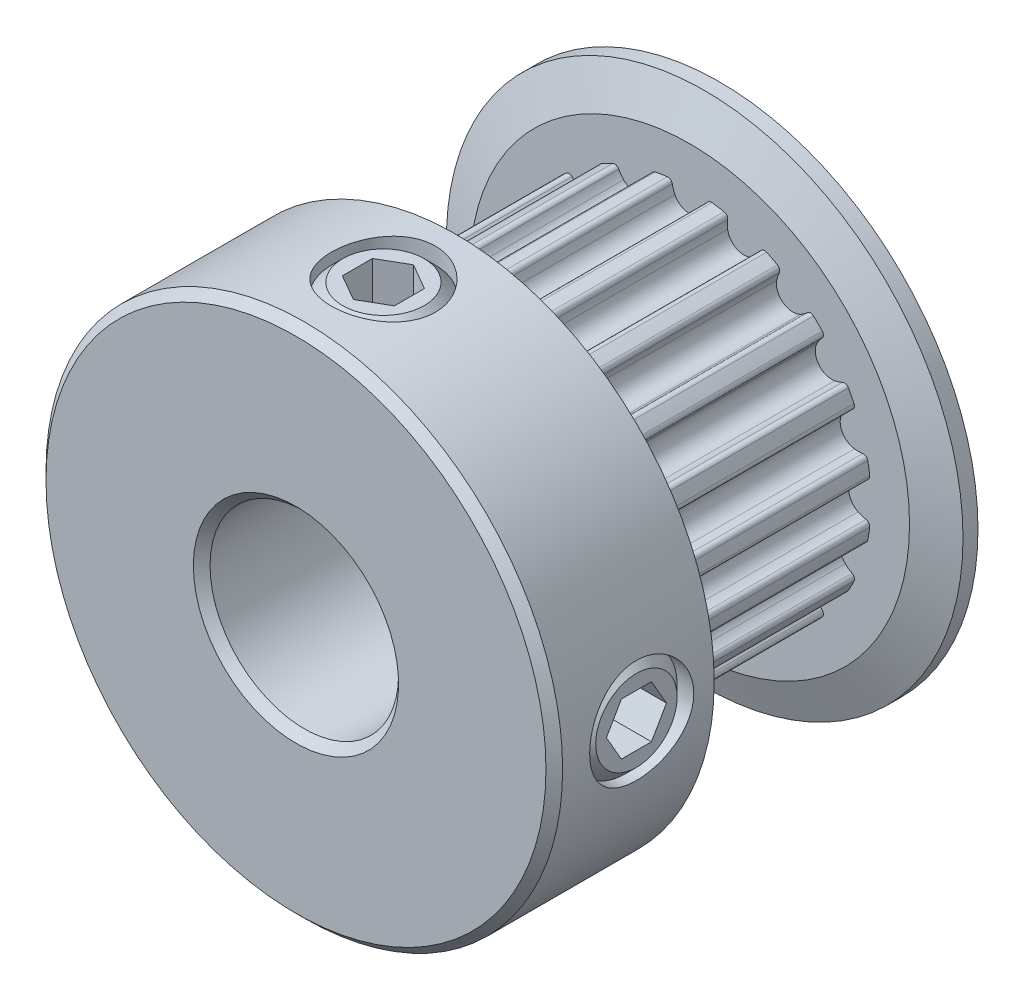
SolidWorks part; units mm, degrees
ref_plane "Front Plane" through (0, 0, 0) normal (0, 0, 1) x (1, 0, 0)
ref_plane "Top Plane" through (0, 0, 0) normal (0, 1, 0) x (1, 0, 0)
ref_plane "Right Plane" through (0, 0, 0) normal (1, 0, 0) x (0, 0, -1)
sketch "Sketch1" plane through (0, 0, 0) normal (0, 0, 1) x (1, 0, 0)
  line L1 (-1.7499, 5.3585) -> (1.7499, 5.3585) construction
  line L4 (0, 0) -> (0, 5.3585) construction
  line L5 (0, 5.3585) -> (0, 11.264) construction
  line L6 (0, 6.3625) -> (1.9751, 6.0482) construction
  line L7 (1.9751, 6.0482) -> (2.6648, 5.8229) construction
  line L8 (1.9751, 6.0482) -> (1.7499, 5.3585) construction
  line L9 (-1.9751, 6.0482) -> (-1.7499, 5.3585) construction
  line L10 (-1.8963, 5.8067) -> (-2.841, 8.6995)
  line L11 (-2.841, 8.6995) -> (2.841, 8.6995)
  line L12 (2.841, 8.6995) -> (1.8963, 5.8067)
  circle A0 centre (0, 0) radius 6.3625 construction
  circle A1 centre (0, 0) radius 8.6995 construction
  circle A2 centre (0, 0) radius 6.1085 construction
  arc A3 (-0.4989, 5.6703) -> (0.4989, 5.6703) centre (0, 5.9135) ccw
  arc A4 (-0.4989, 5.6703) -> (-0.5855, 5.9387) centre (0.4, 6.1085) cw
  arc A5 (-1.8963, 5.8067) -> (-0.7518, 6.0621) centre (0, 0) cw
  arc A6 (-0.5855, 5.9387) -> (-0.7518, 6.0621) centre (-0.7333, 5.9132) ccw
  arc A7 (1.8963, 5.8067) -> (0.7518, 6.0621) centre (0, 0) ccw
  arc A8 (0.5855, 5.9387) -> (0.7518, 6.0621) centre (0.7333, 5.9132) cw
  arc A9 (0.4989, 5.6703) -> (0.5855, 5.9387) centre (-0.4, 6.1085) ccw
  point P6 (0, 20.9083)
  point P11 (0, 6.3625)
  point P13 (0, 8.6995)
  point P14 (0, 6.1085)
  dimension "D1" = 9.6444
  dimension "D2" = 4.9015
sketch "Sketch2" plane through (0, 0, 0) normal (1, 0, 0) x (0, 0, -1)
  line L0 (-7.135, 3.175) -> (7.135, 3.175)
  line L1 (-7.135, 3.175) -> (-7.135, 8.6995)
  line L2 (-1.75, 8.6995) -> (-7.135, 8.6995)
  line L3 (-2.255, 3.175) -> (-2.255, 8.6995) construction
  line L4 (-2.255, 8.6995) -> (-1.245, 8.6995) construction
  line L5 (-1.245, 8.6995) -> (-1.245, 6.1085) construction
  line L6 (-1.245, 6.1085) -> (6.125, 6.1085)
  line L7 (6.125, 6.1085) -> (6.125, 8.6995) construction
  line L8 (6.125, 8.6995) -> (7.135, 8.6995) construction
  line L9 (7.135, 8.6995) -> (7.135, 3.175)
  line L10 (-7.135, 0) -> (7.135, 0) construction
  line L11 (6.63, 8.6995) -> (6.125, 7.404)
  line L12 (-1.245, 7.404) -> (-1.75, 8.6995)
  line L14 (-1.245, 7.404) -> (-1.245, 6.1085)
  line L15 (6.125, 6.1085) -> (6.125, 7.404)
  line L16 (6.63, 8.6995) -> (7.135, 8.6995)
  arc A0 (-1.245, 7.404) -> (-1.75, 8.6995) centre (-3.1592, 7.404) ccw construction
  arc A1 (6.125, 7.404) -> (6.63, 8.6995) centre (8.0392, 7.404) cw construction
  point P12 (-1.245, 7.404)
  point P14 (-1.75, 8.6995)
  point P20 (6.125, 7.404)
  point P21 (6.63, 8.6995)
  point P25 (6.125, 0)
  point P26 (-1.245, 0)
  dimension "OA" = 14.27
  dimension "Bore" = 6.35
  dimension "Outside Width" = 8.38
  dimension "Inside Width" = 7.37
revolve "Revolve1" add sketch "Sketch2" angle 360 mid plane about L10
sketch "Sketch3" plane through (0, 0, 0) normal (0, 0, 1) x (1, 0, 0)
  line L6 (2.841, 8.6995) -> (-2.841, 8.6995)
  line L7 (1.8963, 5.8067) -> (2.841, 8.6995)
  line L8 (-2.841, 8.6995) -> (-1.8963, 5.8067)
  line L9 (2.841, 8.6995) -> (-2.841, 8.6995)
  line L10 (1.8963, 5.8067) -> (2.841, 8.6995)
  line L11 (-2.841, 8.6995) -> (-1.8963, 5.8067)
  arc A8 (1.8963, 5.8067) -> (0.7518, 6.0621) centre (0, 0) ccw
  arc A9 (0.7518, 6.0621) -> (0.5855, 5.9387) centre (0.7333, 5.9132) ccw
  arc A10 (0.4989, 5.6703) -> (0.5855, 5.9387) centre (-0.4, 6.1085) ccw
  arc A11 (-0.4989, 5.6703) -> (0.4989, 5.6703) centre (0, 5.9135) ccw
  arc A12 (-0.5855, 5.9387) -> (-0.4989, 5.6703) centre (0.4, 6.1085) ccw
  arc A13 (-0.5855, 5.9387) -> (-0.7518, 6.0621) centre (-0.7333, 5.9132) ccw
  arc A14 (-0.7518, 6.0621) -> (-1.8963, 5.8067) centre (0, 0) ccw
  arc A15 (1.8963, 5.8067) -> (0.7518, 6.0621) centre (0, 0) ccw
  arc A16 (0.7518, 6.0621) -> (0.5855, 5.9387) centre (0.7333, 5.9132) ccw
  arc A17 (0.4989, 5.6703) -> (0.5855, 5.9387) centre (-0.4, 6.1085) ccw
  arc A18 (-0.4989, 5.6703) -> (0.4989, 5.6703) centre (0, 5.9135) ccw
  arc A19 (-0.5855, 5.9387) -> (-0.4989, 5.6703) centre (0.4, 6.1085) ccw
  arc A20 (-0.5855, 5.9387) -> (-0.7518, 6.0621) centre (-0.7333, 5.9132) ccw
  arc A21 (-0.7518, 6.0621) -> (-1.8963, 5.8067) centre (0, 0) ccw
  dimension "D1" = 0
extrude "Cut-Extrude1" cut sketch "Sketch3" against normal up to vertex (6.125 mm away) from vertex up to point (0, 6.1085, -6.125) starting at point (0, 6.1085, 1.245)
pattern_circular "CirPattern1" count 20 over 360 about axis through (0, 0, 7.135) along (0, 0, 1) of "Cut-Extrude1"
sketch "Sketch4" plane through (0, 0, 0) normal (1, 0, 0) x (0, -1, 0)
  line L0 (0, -1.245) -> (0, -7.135) construction
  line L1 (-3.175, -7.135) -> (3.175, -7.135) construction
  line L2 (7.404, -1.245) -> (-7.404, -1.245) construction
  circle A0 centre (0, -4.19) radius 1.7526
extrude "Cut-Extrude2" cut sketch "Sketch4" along normal through all
ref_plane "Plane1" through (0, 0, 4.19) normal (0, 0, 1) x (1, 0, 0)
sketch "Sketch5" plane through (0, 0, 4.19) normal (0, 0, 1) x (1, 0, 0)
  line L0 (0, 0) -> (0, 8.6995) construction
  line L1 (3.175, -1.3716) -> (3.175, 0)
  line L2 (3.556, -1.7526) -> (8.1401, -1.7526)
  line L3 (3.175, 0) -> (8.6995, 0) construction
  line L4 (3.175, 0) -> (8.5211, 0)
  line L5 (8.5211, 0) -> (8.5211, -1.3716)
  line L6 (3.556, -1.7526) -> (3.175, -1.3716)
  line L7 (8.5211, -1.3716) -> (8.1401, -1.7526)
  circle A0 centre (0, 0) radius 8.6995 construction
  circle A1 centre (0, 0) radius 3.175 construction
  point P2 (3.175, -1.7526)
  point P11 (8.5211, -1.7526)
revolve "Revolve2" add sketch "Sketch5" angle 360 mid plane about L4
sketch "Sketch6" plane through (8.5211, 5.3841, 0) normal (-1, 0, 0) x (0, -1, 0)
  line L1 (5.3841, 5.2019) -> (4.5078, 4.6959)
  line L2 (4.5078, 4.6959) -> (4.5078, 3.6841)
  line L3 (4.5078, 3.6841) -> (5.3841, 3.1781)
  line L4 (5.3841, 3.1781) -> (6.2604, 3.6841)
  line L5 (6.2604, 3.6841) -> (6.2604, 4.6959)
  line L6 (6.2604, 4.6959) -> (5.3841, 5.2019)
  circle A0 centre (5.3841, 4.19) radius 0.8763 construction
  dimension "D1" = 1.7526
extrude "Cut-Extrude3" cut sketch "Sketch6" along normal blind 1.3144
pattern_circular "CirPattern3" count 2 over 90 about axis through (0, 0, 7.135) along (0, 0, 1) of "Cut-Extrude2", "Revolve2", "Cut-Extrude3"
chamfer "Chamfer1" distance 0.2807 angle 45 2 edges at (3.175, 0, 7.135) (8.6995, 0, 7.135)
ref_axis "Center Axis 1" through (0, 0, -7.135) along (0, 0, 1)
ref_plane "Contact Plane 1" through (0, 0, 7.135) normal (0, 0, 1) x (1, 0, 0)
ref_plane "Contact Plane 2" through (0, 0, -7.135) normal (0, 0, -1) x (-1, 0, 0)
equation "\"D2@Sketch1\"= \"D1@Sketch1\" / 2"
equation "\"D1@Sketch6\" = \"Set Screw@Sketch4\" / 2"
equation "\"D1@Cut-Extrude3\" = \"D1@Sketch6\"*.75"
